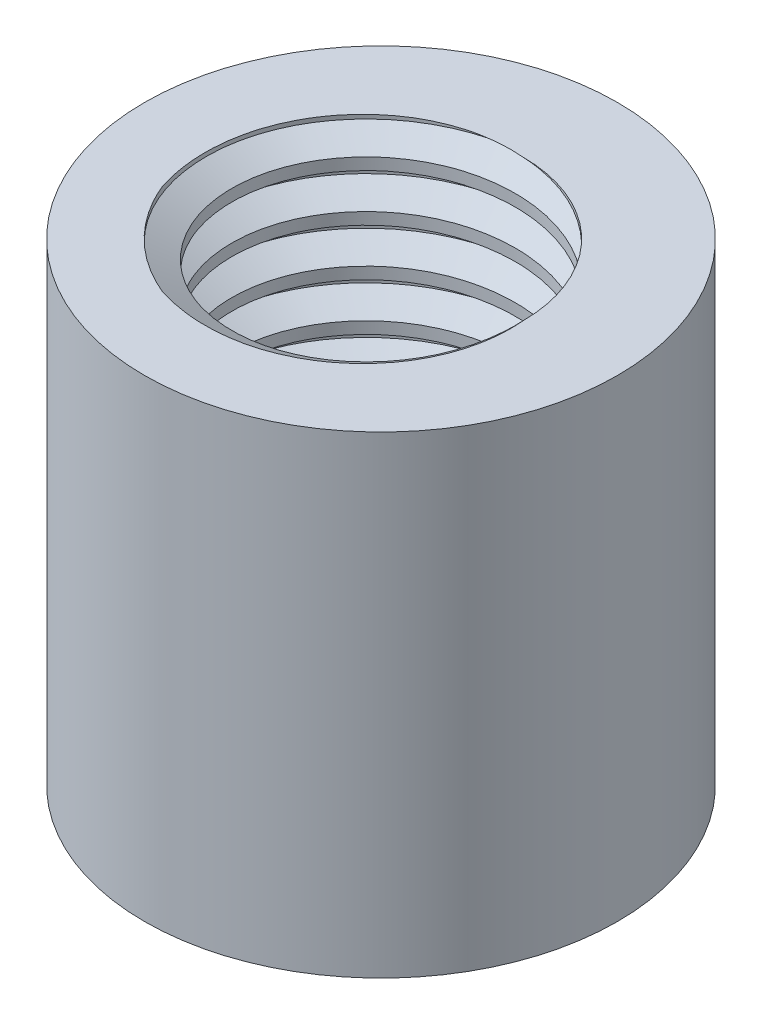
SolidWorks part; units mm, degrees
ref_plane "Front Plane" through (0, 0, 0) normal (0, 0, 1) x (1, 0, 0)
ref_plane "Top Plane" through (0, 0, 0) normal (0, 1, 0) x (1, 0, 0)
ref_plane "Right Plane" through (0, 0, 0) normal (1, 0, 0) x (0, 0, -1)
sketch "Sketch2" plane through (0, 0, 0) normal (0, 1, 0) x (1, 0, 0)
  circle A0 centre (0, 0) radius 3
  circle A1 centre (0, 0) radius 5
  dimension "D1" = 6
  dimension "D2" = 10
extrude "Boss-Extrude1" add sketch "Sketch2" along normal blind 10
sketch "Sketch3" plane through (0, 0, 0) normal (0, 1, 0) x (1, 0, 0)
  circle A0 centre (0, 0) radius 3
extrude "Boss-Extrude2" add sketch "Sketch3" along normal blind 3
thread "Thread1" pitch 1 method cut profile "Thread Profile2" start angle 0, offset 1, length 10, pitch 1, diameter 6
ref_plane "Plane2" through (3, 2, 0) normal (0, 0, 1) x (1, 0, 0)
sketch "Thread Profile2" plane through (3, 2, 0) normal (0, 0, 1) x (1, 0, 0)
  line L0 (0, 0) -> (0, 1) construction
  line L1 (0, 0) -> (0.5413, 0.3125)
  line L2 (0.5413, 0.3125) -> (0.5413, 0.4375)
  line L3 (0.5413, 0.4375) -> (0, 0.75)
  line L4 (0.5413, 0.375) -> (0, 0.375) construction
  line L11 (0, 0) -> (0, 0.75)
  point P2 (0, 0)
  dimension "Pitch" = 1
  dimension "Profile_Angle" = 60
  dimension "Profile_Land" = 0.125
  dimension "Profile_Height" = 0.5413
